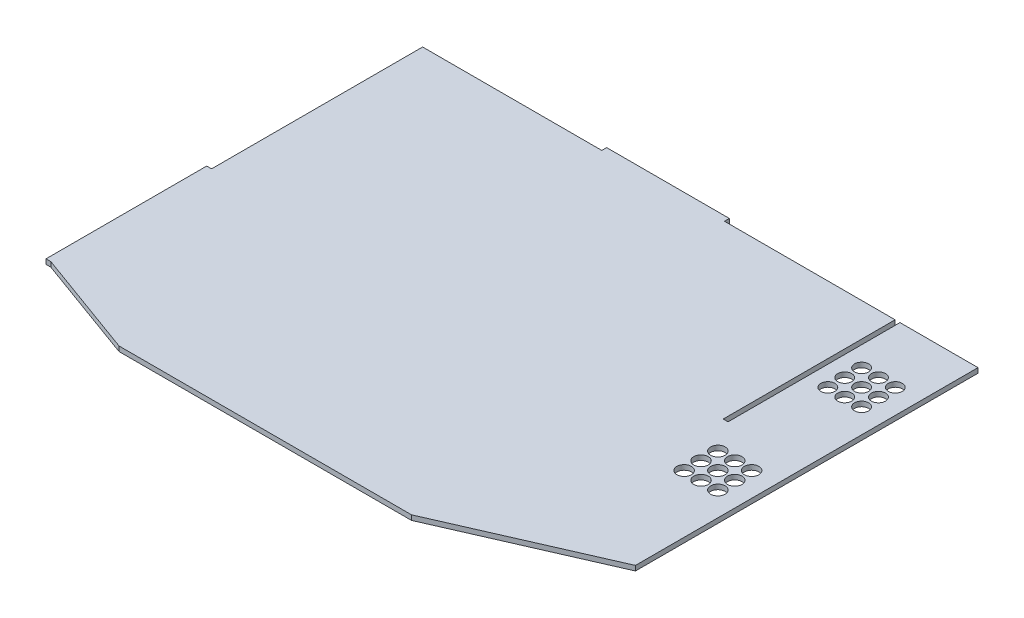
SolidWorks part; units mm, degrees
material "6061-T6 (SS)"
ref_plane "X-Y Datum" through (0, 0, 0) normal (0, 0, 1) x (1, 0, 0)
ref_plane "X-Z Datum" through (0, 0, 0) normal (0, 1, 0) x (1, 0, 0)
ref_plane "Y-Z Datum" through (0, 0, 0) normal (1, 0, 0) x (0, 0, -1)
sketch "Sketch1" plane through (0, 0, 0) normal (0, 0, 1) x (1, 0, 0)
  line L1 (-154.0561, -1.5875) -> (154.0561, -1.5875)
  line L2 (-154.0561, -1.5875) -> (-154.0561, 1.5875)
  line L3 (-154.0561, 1.5875) -> (154.0561, 1.5875)
  line L4 (154.0561, -1.5875) -> (154.0561, 1.5875)
  line L5 (-154.0561, -1.5875) -> (154.0561, 1.5875) construction
  line L6 (-154.0561, 1.5875) -> (154.0561, -1.5875) construction
  point P0 (0, 0)
  dimension "D1" = 3.175
  dimension "D2" = 308.1122
extrude "Boss-Extrude1" add sketch "Sketch1" along normal blind 267.83
sketch "Sketch3" plane through (154.0561, 0, 0) normal (1, 0, 0) x (0, 0, -1)
  line L0 (-267.83, 1.5875) -> (0, 1.5875) construction
  line L1 (-267.83, -1.5875) -> (-112.128, -1.5875)
  line L2 (-267.83, -1.5875) -> (-267.83, 1.5875)
  line L3 (-267.83, 1.5875) -> (-112.128, 1.5875)
  line L4 (-112.128, -1.5875) -> (-112.128, 1.5875)
  dimension "D1" = 155.702
extrude "Boss-Extrude3" add sketch "Sketch3" along normal blind 3.175
sketch "Sketch4" plane through (0, 0, 267.83) normal (0, 0, 1) x (1, 0, 0)
  line L1 (157.2311, -1.5875) -> (208.1047, -1.5875)
  line L2 (157.2311, -1.5875) -> (157.2311, 1.5875)
  line L3 (157.2311, 1.5875) -> (208.1047, 1.5875)
  line L4 (208.1047, -1.5875) -> (208.1047, 1.5875)
  dimension "D1" = 3.175
  dimension "D2" = 50.8737
extrude "Boss-Extrude4" add sketch "Sketch4" against normal blind 267.83
sketch "Sketch6" plane through (0, 1.5875, 0) normal (0, 1, 0) x (1, 0, 0)
  line L0 (106.5047, -267.83) -> (106.5047, -223.38)
  line L1 (208.1047, -267.83) -> (-154.0561, -267.83) construction
  line L2 (208.1047, -223.38) -> (106.5047, -223.38)
  line L3 (208.1047, 0) -> (208.1047, -267.83) construction
  line L4 (106.5047, -267.83) -> (208.1047, -223.38)
  line M9 (-154.0561, -267.83) -> (208.1047, -267.83)
  line M10 (208.1047, -267.83) -> (208.1047, 0)
  dimension "D1" = 44.45
  dimension "D2" = 101.6
extrude "Cut-Extrude1" cut sketch "Sketch6" against normal through all contours L4 M9 M10 region at (174.2381, 1.5875, 253.0133)
sketch "Sketch8" plane through (0, 0, 0) normal (0, 0, -1) x (-1, 0, 0)
  line L1 (37.216, 1.5875) -> (-42.784, 1.5875)
  line L2 (37.216, 1.5875) -> (37.216, -1.5875)
  line L3 (37.216, -1.5875) -> (-42.784, -1.5875)
  line L4 (-42.784, 1.5875) -> (-42.784, -1.5875)
extrude "Boss-Extrude6" add sketch "Sketch8" along normal blind 3.175
sketch "Sketch11" plane through (0, -1.5875, 0) normal (0, -1, 0) x (1, 0, 0)
  line L0 (-84.2061, 267.83) -> (-84.2061, 242.43)
  line L1 (-154.0561, 267.83) -> (106.5047, 267.83) construction
  line L2 (-154.0561, 242.43) -> (-84.2061, 242.43)
  line L3 (-154.0561, 267.83) -> (-154.0561, 0) construction
  line L4 (-154.0561, 242.43) -> (-84.2061, 267.83)
  line M4 (-154.0561, 267.83) -> (-154.0561, 0)
  line M18 (106.5047, 267.83) -> (-154.0561, 267.83)
  dimension "D1" = 69.85
  dimension "D2" = 25.4
extrude "Cut-Extrude3" cut sketch "Sketch11" against normal through all contours L4 M4 M18 region at (-130.7727, -1.5875, 259.3633)
sketch "Sketch13" plane through (-154.0561, 0, 0) normal (-1, 0, 0) x (0, 0, 1)
  line L1 (137.65, -1.598) -> (242.43, -1.598)
  line L2 (137.65, -1.598) -> (137.65, 1.5875)
  line L3 (137.65, 1.5875) -> (242.43, 1.5875)
  line L4 (242.43, -1.598) -> (242.43, 1.5875)
extrude "Boss-Extrude7" add sketch "Sketch13" along normal blind 3.175
sketch "Sketch14" plane through (0, 1.5875, 0) normal (0, 1, 0) x (1, 0, 0)
  circle A2 centre (192.4141, -153.9343) radius 4.7383
extrude "Cut-Extrude4" cut sketch "Sketch14" against normal through all
pattern_linear "LPattern1" count 3 spacing 11 along (-1, 0, 0) of "Cut-Extrude4"
pattern_linear "LPattern2" count 3 spacing 11 along (0, 0, -1) of "LPattern1"
sketch "Sketch15" plane through (0, 1.5875, 0) normal (0, 1, 0) x (1, 0, 0)
  line L0 (208.1047, 0) -> (157.2311, 0) construction
  circle A1 centre (170.2898, -38.1) radius 4.5777
  dimension "D1" = 38.1
extrude "Cut-Extrude5" cut sketch "Sketch15" against normal through all
pattern_linear "LPattern3" count 3 spacing 11 along (1, 0, 0) of "Cut-Extrude5"
pattern_linear "LPattern4" count 3 spacing 11 along (0, 0, 1) of "LPattern3"
